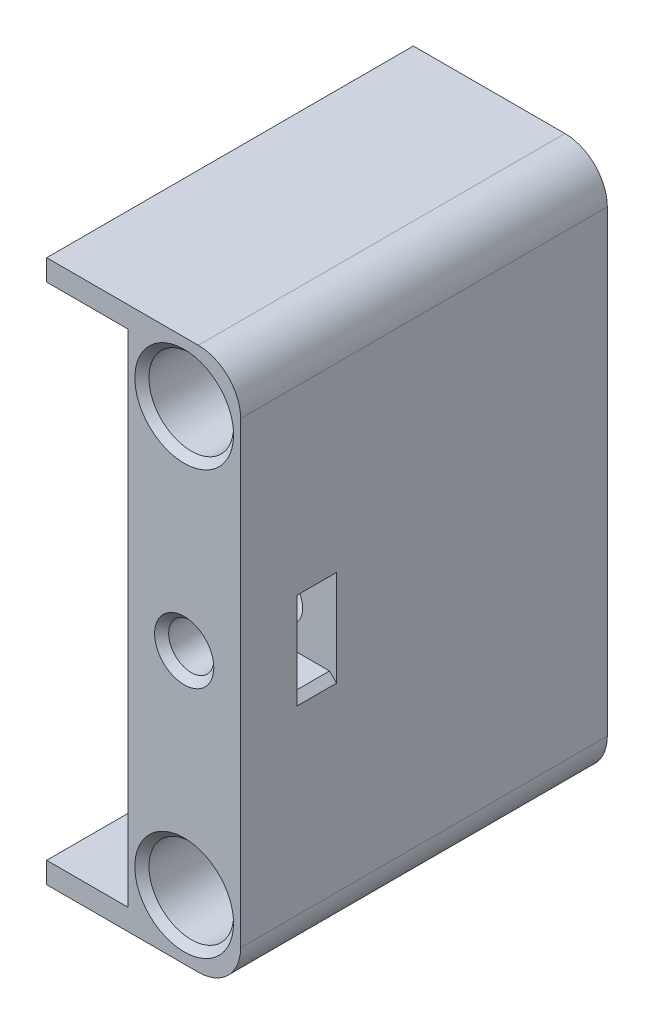
SolidWorks part; units mm, degrees
ref_plane "Front Plane" through (0, 0, 0) normal (0, 0, 1) x (1, 0, 0)
ref_plane "Top Plane" through (0, 0, 0) normal (0, 1, 0) x (1, 0, 0)
ref_plane "Right Plane" through (0, 0, 0) normal (1, 0, 0) x (0, 0, -1)
sketch "Sketch1" plane through (0, 0, 0) normal (0, 0, 1) x (1, 0, 0)
  line L0 (-5.75, -17.75) -> (-5.75, -19.25)
  line L1 (-5.75, 19.25) -> (8, 19.25)
  line L2 (-5.75, 19.25) -> (-5.75, 17.75)
  line L3 (-5.75, -19.25) -> (8, -19.25)
  line L4 (8, 19.25) -> (8, -19.25)
  line L5 (-5.75, 17.75) -> (0, 17.75)
  line L6 (4, 15) -> (4, -15) construction
  line L7 (-5.75, -17.75) -> (0, -17.75)
  line L8 (0, 17.75) -> (0, -17.75)
  circle A0 centre (4, 15) radius 1.6
  circle A1 centre (4, 0) radius 1.6
  circle A2 centre (4, -15) radius 1.6
  point P6 (0, 0)
  point P12 (4, 0)
  dimension "D7" = 3.2
  dimension "D1" = 35.5
  dimension "D2" = 8
  dimension "D3" = 5.75
  dimension "D4" = 1.5
  dimension "D5" = 4
  dimension "D6" = 30
extrude "Boss-Extrude1" add sketch "Sketch1" along normal blind 26
sketch "Sketch2" plane through (0, 0, 26) normal (0, 0, 1) x (1, 0, 0)
  circle A0 centre (4, 15) radius 3
  circle A1 centre (4, -15) radius 3
  dimension "D1" = 6
extrude "Cut-Extrude1" cut sketch "Sketch2" against normal blind 19
sketch "Sketch3" plane through (0, 0, 26) normal (0, 0, 1) x (1, 0, 0)
  line L1 (0, 2.9) -> (8, 2.9)
  line L2 (0, 2.9) -> (0, -2.9)
  line L3 (0, -2.9) -> (8, -2.9)
  line L4 (8, 2.9) -> (8, -2.9)
  line L5 (8, -19.25) -> (8, 19.25) construction
  line L6 (4, 0) -> (8, 0) construction
  line L8 (0, 17.75) -> (0, -17.75) construction
  dimension "D1" = 5.8
extrude "Cut-Extrude2" cut sketch "Sketch3" against normal blind 2.8 from offset 4 offset against normal yes
fillet "Fillet1" radius 3 2 edges at (8, -19.25, 13) (8, 19.25, 13)
chamfer "Chamfer1" distance 0.5 angle 45 8 edges at (5.6, 15, 0) (5.6, 0, 0) (5.6, -15, 0) (7, -15, 26) (7, 15, 26) (5.6, 0, 26) (8, 2.9, 20.6) (8, -2.9, 20.6)
